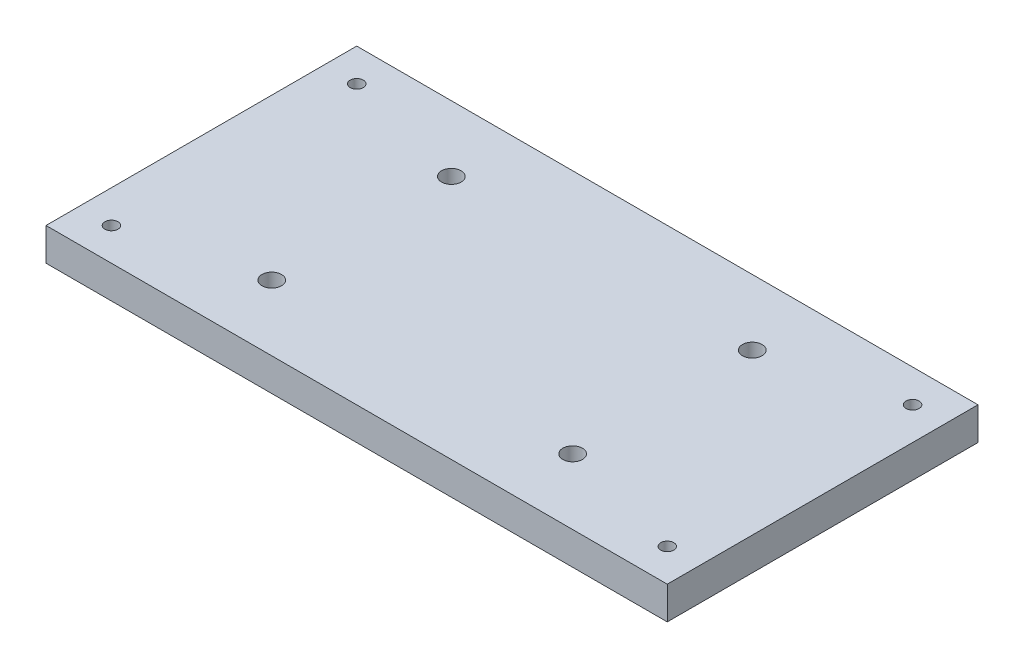
SolidWorks part; units mm, degrees
note: The reader was unsure of these and kept them because the rebuilt part matched: shared geometry of "Sketch2<4>".
ref_plane "Front Plane" through (0, 0, 0) normal (0, 0, 1) x (1, 0, 0)
ref_plane "Top Plane" through (0, 0, 0) normal (0, 1, 0) x (1, 0, 0)
ref_plane "Right Plane" through (0, 0, 0) normal (1, 0, 0) x (0, 0, -1)
sketch "Sketch2" plane through (0, 0, 0) normal (0, 1, 0) x (1, 0, 0)
  line L0 (-101.3673, 42.2915) -> (-91.3673, 42.2915)
  line L1 (88.5827, 42.2915) -> (-101.3673, 42.2915)
  line L2 (-91.3673, 42.2915) -> (-91.3673, 32.2915)
  line L3 (88.5827, -52.7085) -> (-101.3673, -52.7085)
  line L4 (-101.3673, 42.2915) -> (-101.3673, -52.7085)
  line L5 (88.5827, 42.2915) -> (88.5827, -52.7085)
  line L6 (-6.3923, 42.2915) -> (-6.3923, -52.7085)
  line L7 (-101.3673, -5.2085) -> (88.5827, -5.2085)
  line L8 (-6.3923, -5.2085) -> (-6.3923, 29.1146)
  line L13 (-6.3923, -5.2085) -> (-6.3923, 22.2515)
  line L14 (39.6077, 22.2515) -> (-52.3923, 22.2515)
  line L15 (39.6077, -32.6685) -> (-52.3923, -32.6685)
  circle A0 centre (-91.3673, 32.2915) radius 2
  circle A1 centre (-91.3673, -42.7085) radius 2
  circle A2 centre (78.5827, -42.7085) radius 2
  circle A3 centre (78.5827, 32.2915) radius 2
  circle A9 centre (-52.3923, 22.2515) radius 3
  circle A10 centre (-52.3923, -32.6685) radius 3
  circle A11 centre (39.6077, 22.2515) radius 3
  circle A12 centre (39.6077, -32.6685) radius 3
  point P25 (-6.3923, -32.6685)
extrude "Boss-Extrude1" add sketch "Sketch2" along normal blind 10
extrude "Cut-Extrude1" cut sketch "Sketch2<4>" along normal blind 35 contours A12
sketch "Sketch2<4>" plane through (0, 0, 0) normal (0, 1, 0) x (1, 0, 0) same geometry as "Sketch2"
